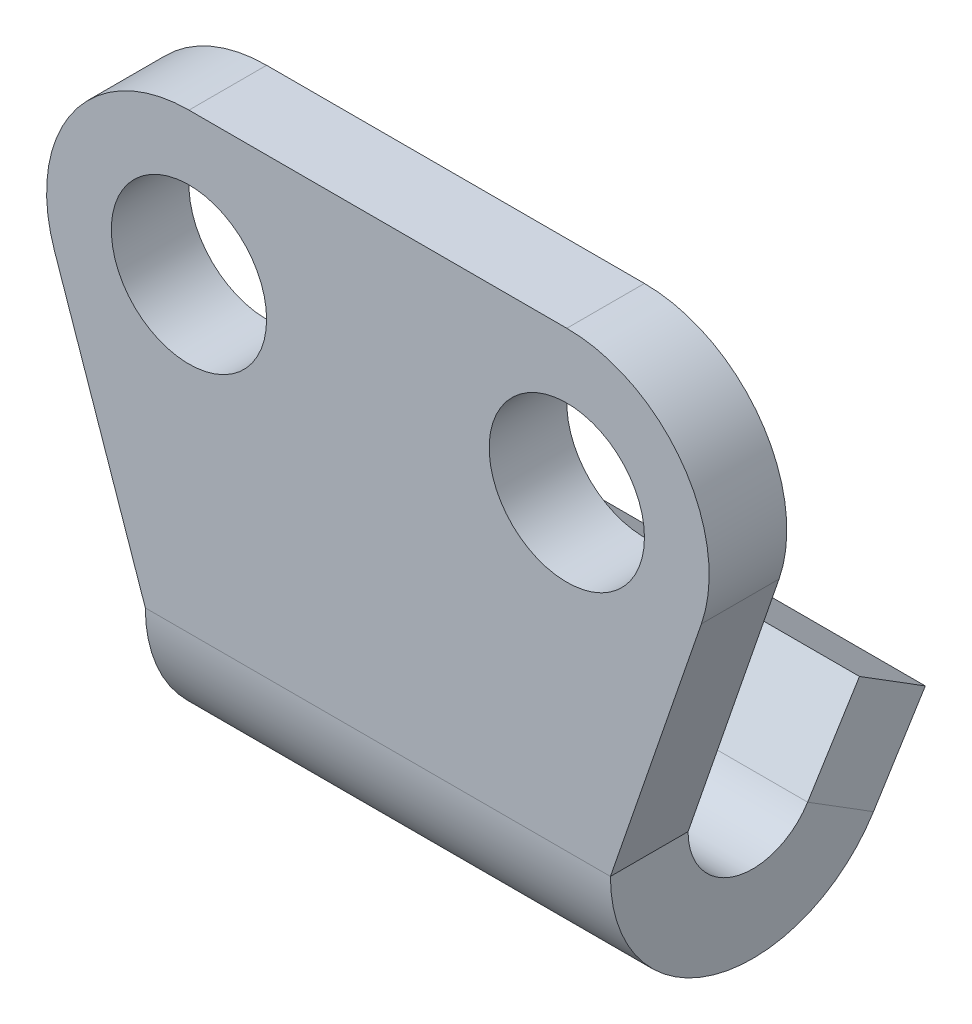
SolidWorks part; units mm, degrees
note: The reader was unsure of these and kept them because the rebuilt part matched: flange length of "Bordo-Flangia3".
ref_plane "Piano frontale" through (0, 0, 0) normal (0, 0, 1) x (1, 0, 0)
ref_plane "Piano superiore" through (0, 0, 0) normal (0, 1, 0) x (1, 0, 0)
ref_plane "Piano destro" through (0, 0, 0) normal (1, 0, 0) x (0, 0, -1)
sketch "Schizzo2" plane through (0, 0, 0) normal (0, 0, 1) x (1, 0, 0)
  line L1 (-7.3, 0) -> (7.3, 0)
  line L4 (0, 0) -> (0, -17.5) construction
  line L5 (-8.985, -17.5) -> (-12.5004, -7.2906)
  line L6 (8.985, -17.5) -> (12.5004, -7.2906)
  line L10 (8.985, -17.5) -> (-8.985, -17.5)
  circle A0 centre (-7.3, -5.5) radius 3
  circle A1 centre (7.3, -5.5) radius 3
  arc A2 (-7.3, 0) -> (-12.5004, -7.2906) centre (-7.3, -5.5) ccw
  arc A3 (12.5004, -7.2906) -> (7.3, 0) centre (7.3, -5.5) ccw
  dimension "D7" = 6
  dimension "D8" = 6
  dimension "D9" = 11
  dimension "D10" = 11
  dimension "D2" = 14.6
  dimension "D3" = 38
  dimension "D4" = 5.5
  dimension "D5" = 17.5
  dimension "D6" = 7.3
  dimension "D11" = 8.985
base flange "Base-Flangia1" sketch "Schizzo2" thickness 3 reverse thickness direction no parameters "D1"=0.7366
sketch "Schizzo15" plane through (0, 0, 0) normal (1, 0, 0) x (0, 0, -1)
  line L1 (8, -17.5) -> (3, -17.5) construction
  line L3 (9.6232, -15.6192) -> (7.6201, -18.8248)
  line L4 (3, -17.5) -> (3, -7.2906) construction
  arc A0 (3, -17.5) -> (7.6201, -18.8248) centre (5.5, -17.5) ccw
  dimension "D1" = 5
  dimension "D2" = 3.78
  dimension "D3" = 32
edge flange "Bordo-Flangia3" sketch "Schizzo23" flange angle 32 flange length 15 flange position bend outside bend radius 2.5 thickness 3 relief rectangular parameters "D6"=10
sketch "Schizzo23" plane through (0, -17.5, -3) normal (0, -0.5299, -0.848) x (-1, 0, 0)
  line L2 (-8.985, 0) -> (-8.985, 15)
  line L3 (-8.985, 15) -> (8.985, 15)
  line L4 (8.985, 15) -> (8.985, 0)
  line L7 (8.985, 0) -> (-8.985, 0) construction
  line L8 (8.985, 0) -> (-8.985, 0)
bend "PiegaturaBordo2" bend radius 2.5 bend angle 148 parameters "D5"=1
sketch "Schizzo25" plane through (8.985, 0, 0) normal (1, 0, 0) x (0, 0, -1)
  line L0 (9.6232, -15.6192) -> (12.1674, -17.2089) construction
  line L1 (10.9488, -13.4978) -> (7.6201, -18.8248) construction
  line L2 (13.4929, -15.0876) -> (10.1643, -20.4146) construction
  line L3 (7.6201, -18.8248) -> (10.1643, -20.4146) construction
  line L4 (9.6232, -15.6192) -> (10.9488, -13.4978)
  line L5 (10.9488, -13.4978) -> (13.4929, -15.0876)
  line L6 (13.4929, -15.0876) -> (12.1674, -17.2089)
  line L7 (12.1674, -17.2089) -> (9.6232, -15.6192)
  dimension "D1" = 3.78
extrude "Taglio-Estrusione1" cut sketch "Schizzo25" against normal through all normal cut yes
sketch "Linee di piegatura1" [suppressed] plane through (0, 0, 0) normal (0, 1, 0) x (1, 0, 0)
sketch "Casella di contorno1" [suppressed] plane through (0, 0, 0) normal (0, 1, 0) x (1, 0, 0)
sheet metal parameters "Lamiera1" thickness 3 parameters "D1"=0.7366
flat pattern "Ripetizione piatta1" [suppressed]
sketch "Linee di piegatura2" plane through (0, 0, 0) normal (0, 1, 0) x (1, 0, 0)
sketch3d "Casella di contorno2" [suppressed]
  line L0 (-5.4999, 5.5, 0) -> (20.0999, 5.5, 0) construction
  line L1 (-5.4999, -12, 0) -> (20.0999, -12, 0) construction
  line L2 (-5.4999, 5.5, 0) -> (-5.4999, -12, 0) construction
  line L3 (20.0999, 5.5, 0) -> (20.0999, -12, 0) construction
sheet metal parameters "Lamiera3" thickness 3 parameters "D1"=0.7366
flat pattern "Ripetizione piatta1"
sketch "Linee di piegatura2" plane through (0, 0, 0) normal (0, 0, 1) x (1, 0, 0)
  line L0 (-8.985, -22.6662) -> (8.985, -22.6662) construction
  line L1 (-8.985, -22.6662) -> (8.985, -22.6662) construction
sketch3d "Casella di contorno2" [suppressed]
  line L0 (20.0999, -28.6138, 0) -> (20.0999, 5.5, 0) construction
  line L1 (-5.4999, -28.6138, 0) -> (-5.4999, 5.5, 0) construction
  line L2 (20.0999, -28.6138, 0) -> (-5.4999, -28.6138, 0) construction
  line L3 (20.0999, 5.5, 0) -> (-5.4999, 5.5, 0) construction
bend of the flat pattern "Appiattito-<PiegaturaBordo2>1"
sheet metal parameters "Lamiera4" thickness 3 parameters "D1"=0.7366
flat pattern "Ripetizione piatta1"
sketch "Linee di piegatura2" plane through (0, 0, 0) normal (0, 0, 1) x (1, 0, 0)
  line L0 (-8.985, -22.6662) -> (8.985, -22.6662) construction
  line L1 (-8.985, -22.6662) -> (8.985, -22.6662) construction
sketch3d "Casella di contorno2" [suppressed]
  line L0 (20.0999, -26.1123, 0) -> (20.0999, 5.5, 0) construction
  line L1 (-5.4999, -26.1123, 0) -> (-5.4999, 5.5, 0) construction
  line L2 (20.0999, -26.1123, 0) -> (-5.4999, -26.1123, 0) construction
  line L3 (20.0999, 5.5, 0) -> (-5.4999, 5.5, 0) construction
bend of the flat pattern "Appiattito-<PiegaturaBordo2>1"
